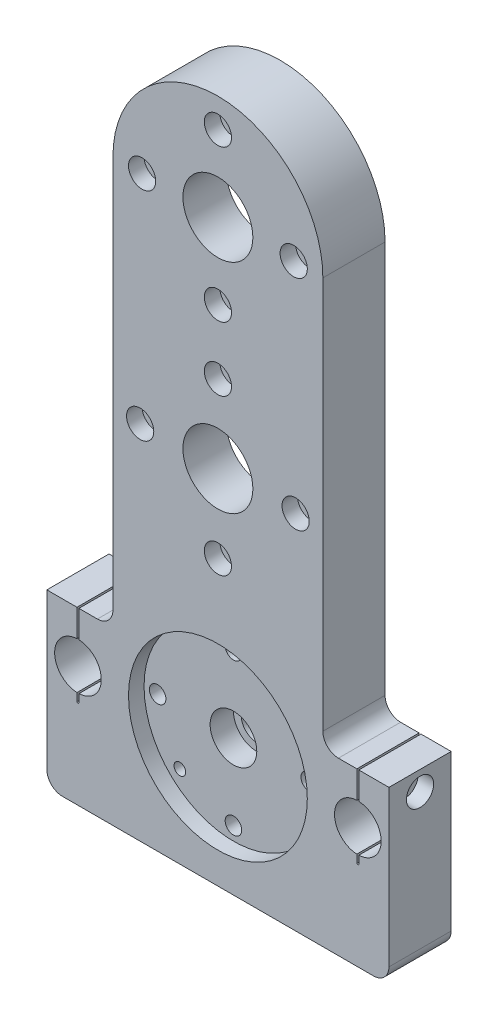
SolidWorks part; units mm, degrees
material "6061 Alloy"
ref_plane "Front" through (0, 0, 0) normal (0, 0, 1) x (1, 0, 0)
ref_plane "Top" through (0, 0, 0) normal (0, 1, 0) x (1, 0, 0)
ref_plane "Right" through (0, 0, 0) normal (1, 0, 0) x (0, 0, -1)
ref_axis "Axis" through (0, 0, -80.9) along (0, 0, 1)
sketch "Bolt circle" plane through (0, 0, 0) normal (0, 0, 1) x (1, 0, 0)
  line L0 (0, 36.5125) -> (0, 25.4) construction
  line L1 (-42.8625, 88.9) -> (-42.8625, -77.7875)
  line L2 (0, 114.3) -> (0, 125.4125) construction
  line L3 (42.8625, 88.9) -> (42.8625, -77.7875)
  line L7 (42.8625, -77.7875) -> (69.85, -77.7875)
  line L12 (-42.8625, -77.7875) -> (-69.85, -77.7875)
  line L30 (69.85, -77.7875) -> (69.85, -147.6375)
  line L31 (69.85, -147.6375) -> (-69.85, -147.6375)
  line L34 (-69.85, -77.7875) -> (-69.85, -147.6375)
  line L35 (0, 0) -> (0, -147.6375) construction
  circle A0 centre (0, 0) radius 36.5125 construction
  circle A1 centre (0, 0) radius 25.4 construction
  circle A2 centre (0, 0) radius 30.9562 construction
  arc A3 (-42.8625, 88.9) -> (42.8625, 88.9) centre (0, 88.9) cw
  circle A4 centre (0, 88.9) radius 14.2748
  circle A5 centre (0, 88.9) radius 36.5125 construction
  circle A6 centre (0, 88.9) radius 25.4 construction
  circle A7 centre (0, 0) radius 14.2748
  circle A8 centre (0, -98.425) radius 36.5125 construction
  circle A9 centre (0, -98.425) radius 6.35
  circle A10 centre (0, 88.9) radius 30.9562 construction
  point P0 (0, -36.5125)
  point P7 (0, 30.9562)
  point P9 (0, -134.9375)
  point P20 (0, 119.8562)
  dimension "D1" = 73.025
  dimension "D2" = 50.8
  dimension "D3" = 69.85
  dimension "D12" = 139.7
  dimension "D5" = 26.9875
  dimension "D13" = 28.5496
  dimension "D18" = 12.7
  dimension "D6" = 88.9
  dimension "D8" = 73.025
  dimension "D9" = 28.5496
  dimension "D10" = 50.8
  dimension "D4" = 98.425
  dimension "D7" = 85.725
  dimension "D17" = 12.7
extrude "Base" add sketch "Bolt circle" along normal mid plane 25.4
hole_wizard "Structure tube connection counterbore" positions "Sketch15" profile "Sketch14" counterbore size "1/4" standard "Ansi Inch" end condition through all
sketch "Sketch15" plane through (0, 0, -12.7) normal (0, 0, -1) x (-1, 0, 0)
  circle A0 centre (0, -98.425) radius 30.9563 construction
  point P1 (0, -67.4688)
  dimension "D1" = 61.9125
sketch "Sketch14" plane through (0, -67.4688, -12.7) normal (1, 0, 0) x (0, 1, 0)
  line L0 (0, 0) -> (0, 25.4)
  line L1 (0, 25.4) -> (3.3782, 25.4)
  line L3 (3.3782, 25.4) -> (3.3782, 6.35)
  line L4 (3.3782, 6.35) -> (5.5562, 6.35)
  line L5 (5.5562, 6.35) -> (5.5562, 0)
  line L7 (5.5562, 0) -> (0, 0)
  line L11 (0, -6.35) -> (0, 107.95) construction
  dimension "Thru Hole Dia." = 6.7564
  dimension "Thru Hole Depth" = 25.4
  dimension "C'Bore Dia." = 11.1125
  dimension "C'Bore Depth" = 6.35
pattern_circular "Structure tube connection counterbore pattern" count 4 over 360 about axis through (0, -98.425, 12.7) along (0, 0, -1) of "Structure tube connection counterbore"
hole_wizard "Spindle connection counterbore" positions "Sketch11" profile "Sketch10" counterbore size "1/4" standard "Ansi Inch" end condition through all
sketch "Sketch11" plane through (0, 0, 12.7) normal (0, 0, 1) x (1, 0, 0)
  circle A0 centre (0, 0) radius 31.75 construction
  point P0 (0, 31.75)
  dimension "D1" = 63.5
sketch "Sketch10" plane through (0, 31.75, 12.7) normal (1, 0, 0) x (0, -1, 0)
  line L0 (0, 0) -> (0, 25.4)
  line L1 (0, 25.4) -> (3.3782, 25.4)
  line L3 (3.3782, 25.4) -> (3.3782, 6.35)
  line L4 (3.3782, 6.35) -> (5.5562, 6.35)
  line L5 (5.5562, 6.35) -> (5.5562, 0)
  line L7 (5.5562, 0) -> (0, 0)
  line L11 (0, -6.35) -> (0, 107.95) construction
  dimension "Thru Hole Dia." = 6.7564
  dimension "Thru Hole Depth" = 25.4
  dimension "C'Bore Dia." = 11.1125
  dimension "C'Bore Depth" = 6.35
pattern_circular "Spindle connection counterbore pattern" count 4 over 360 about axis through (0, 0, 12.7) along (0, 0, -1) of "Spindle connection counterbore"
sketch "Sketch16" plane through (0, 0, 12.7) normal (0, 0, 1) x (1, 0, 0)
  circle A0 centre (0, -98.425) radius 36.5125
  dimension "D1" = 73.025
extrude "Structure tube mounting pocket" cut sketch "Sketch16" against normal blind 6.35
sketch "Sketch17" plane through (0, 0, -12.7) normal (0, 0, -1) x (-1, 0, 0)
  circle A0 centre (0, 0) radius 36.5125
  circle A1 centre (0, -98.425) radius 36.5125 construction
  dimension "D1" = 73.025
extrude "Spindle mounting pocket" cut sketch "Sketch17" against normal blind 7.62
sketch "Sketch18" plane through (0, 0, 6.35) normal (0, 0, 1) x (1, 0, 0)
  circle A0 centre (0, -98.425) radius 9.525
  dimension "D1" = 19.05
extrude "Lead screw through hole" cut sketch "Sketch18" against normal blind 9.525
sketch "Sketch20" plane through (0, 0, 12.7) normal (0, 0, 1) x (1, 0, 0)
  line L1 (57.15, -98.425) -> (-57.15, -98.425) construction
  circle A0 centre (57.15, -98.425) radius 9.525
  circle A1 centre (-57.15, -98.425) radius 9.525
  dimension "D2" = 114.3
  dimension "D3" = 19.05
extrude "Rail mounting pilot_holes" cut sketch "Sketch20" against normal through all
sketch "Sketch27" plane through (0, 0, 6.35) normal (0, 0, 1) x (1, 0, 0)
  line L0 (20.6813, -74.3354) -> (19.6028, -75.5003)
  line L1 (24.176, -77.571) -> (23.0974, -78.7359)
  line L2 (21.8894, -76.5356) -> (-21.8894, -120.3144) construction
  line L3 (20.1421, -74.9178) -> (23.6367, -78.1534) construction
  line L4 (50, 0) -> (-50, 0) construction
  circle A0 centre (-21.8894, -120.3144) radius 2.3813
  arc A1 (24.176, -77.571) -> (20.6813, -74.3354) centre (22.4286, -75.9532) ccw
  arc A2 (23.0974, -78.7359) -> (19.6028, -75.5003) centre (21.3501, -77.1181) cw
  circle A3 centre (21.8894, -76.5356) radius 2.3813 construction
  circle A4 centre (0, -98.425) radius 30.9563 construction
  point P10 (20.1421, -74.9178)
  dimension "D2" = 45
  dimension "D3" = 4.7625
  dimension "D1" = 1.5875
extrude "Alignment_features" cut sketch "Sketch27" against normal blind 6.35
fillet "Generic_rounding_fillet" radius 6.35 4 edges at (42.8625, -77.7875, 0) (-42.8625, -77.7875, 0) (-69.85, -147.6375, 0) (69.85, -147.6375, 0)
sketch "Sketch21" plane through (0, -147.6375, 0) normal (0, -1, 0) x (1, 0, 0)
  line L0 (69.85, 0) -> (-69.85, 0) construction
  line L1 (69.85, 12.7) -> (69.85, -12.7) construction
  line L2 (-69.85, 12.7) -> (-69.85, -12.7) construction
  line L3 (0, -12.7) -> (0, 12.7) construction
  line L4 (-63.5, -12.7) -> (63.5, -12.7) construction
  line L5 (-63.5, 12.7) -> (63.5, 12.7) construction
  circle A0 centre (57.15, 0) radius 4.7625
  circle A1 centre (-57.15, 0) radius 4.7625
  dimension "D1" = 9.525
  dimension "D2" = 114.3
extrude "Point_mount_bores" [suppressed] cut sketch "Sketch21" against normal blind 6.35
sketch "Sketch22" plane through (0, 0, 12.7) normal (0, 0, 1) x (1, 0, 0)
  line L0 (69.85, -77.7875) -> (49.2125, -77.7875) construction
  line L1 (56.7531, -77.7875) -> (57.5469, -77.7875)
  line L2 (56.7531, -77.7875) -> (56.7531, -111.125)
  line L3 (57.15, -111.125) -> (57.15, -98.425) construction
  line L4 (57.5469, -77.7875) -> (57.5469, -111.125)
  line L5 (0, -147.6375) -> (0, 131.7625) construction
  line L6 (-63.5, -147.6375) -> (63.5, -147.6375) construction
  line L7 (-57.15, -111.125) -> (-57.15, -98.425) construction
  line L8 (-57.5469, -77.7875) -> (-57.5469, -111.125)
  line L9 (-56.7531, -77.7875) -> (-56.7531, -111.125)
  line L10 (-56.7531, -77.7875) -> (-57.5469, -77.7875)
  arc A0 (56.7531, -111.125) -> (57.5469, -111.125) centre (57.15, -111.125) ccw
  arc A2 (-56.7531, -111.125) -> (-57.5469, -111.125) centre (-57.15, -111.125) cw
  arc A3 (42.8625, 88.9) -> (-42.8625, 88.9) centre (0, 88.9) ccw construction
  dimension "D1" = 0.7937
  dimension "D2" = 12.7
extrude "Flexure_clamp_slits" cut sketch "Sketch22" against normal through all
hole_wizard "Flexure_clamp_counterbore" positions "Sketch24" profile "Sketch23" counterbore size "1/4" standard "Ansi Inch" end condition up to next
sketch "Sketch24" plane through (69.85, 0, 0) normal (1, 0, 0) x (0, 0, -1)
  line L0 (0, 50) -> (0, -50) construction
  line L1 (-12.7, -77.7875) -> (12.7, -77.7875) construction
  point P0 (0, -85.725)
  dimension "D1" = 7.9375
sketch "Sketch23" plane through (69.85, -85.725, 0) normal (0, 1, 0) x (0, 0, -1)
  line L0 (0, 0) -> (0, 12.3031)
  line L1 (0, 12.3031) -> (3.3782, 12.3031)
  line L3 (3.3782, 12.3031) -> (3.3782, 6.35)
  line L4 (3.3782, 6.35) -> (5.5562, 6.35)
  line L5 (5.5562, 6.35) -> (5.5562, 0)
  line L7 (5.5562, 0) -> (0, 0)
  line L11 (0, -6.35) -> (0, 107.95) construction
  dimension "Thru Hole Dia." = 6.7564
  dimension "Thru Hole Depth" = 12.3031
  dimension "C'Bore Dia." = 11.1125
  dimension "C'Bore Depth" = 6.35
hole_wizard "Flexure_clamp_threads" positions "Sketch26" profile "Sketch25" tap size "1/4-20" standard "Ansi Inch"
sketch "Sketch26" plane through (56.7531, 0, 0) normal (1, 0, 0) x (0, 0, -1)
  point P1 (0, -85.725)
sketch "Sketch25" plane through (56.7531, -85.725, 0) normal (0, 1, 0) x (0, 0, -1)
  line L0 (0, 0) -> (0, 18.0438)
  line L1 (0, 18.0438) -> (2.5527, 16.51)
  line L2 (2.5527, 16.51) -> (2.5527, 0)
  line L5 (2.5527, 0) -> (0, 0)
  line L10 (0, 18.0438) -> (-2.5527, 16.51) construction
  line L11 (0, -6.35) -> (0, 107.95) construction
  dimension "Tap Drill Dia." = 5.1054
  dimension "Tap Drill Depth" = 16.51
  dimension "Drill Angle" = 118
cosmetic thread "Hole Thread2" parameters "D1"=12.7, "D2"=6.35
mirror "Flexure_clamp_fastener_holes" about plane through (0, 0, 0) normal (1, 0, 0) of "Flexure_clamp_counterbore", "Flexure_clamp_threads"
hole_wizard "wood_spindle_CBORE" positions "Sketch28" profile "Sketch29" counterbore size "1/4" standard "ANSI Inch" end condition through all
sketch "Sketch28" plane through (0, 0, 12.7) normal (0, 0, 1) x (1, 0, 0)
  point P0 (0, 119.8562)
sketch "Sketch29" plane through (0, 119.8562, 12.7) normal (1, 0, 0) x (0, -1, 0)
  line L0 (0, 0) -> (0, 25.4)
  line L1 (0, 25.4) -> (3.3782, 25.4)
  line L3 (3.3782, 25.4) -> (3.3782, 6.35)
  line L4 (3.3782, 6.35) -> (5.5562, 6.35)
  line L5 (5.5562, 6.35) -> (5.5562, 0)
  line L7 (5.5562, 0) -> (0, 0)
  line L11 (0, -6.35) -> (0, 107.95) construction
  dimension "Thru Hole Dia." = 6.7564
  dimension "Thru Hole Depth" = 25.4
  dimension "C'Bore Dia." = 11.1125
  dimension "C'Bore Depth" = 6.35
pattern_circular "CirPattern1" count 4 over 360 about axis through (0, 88.9, 12.7) along (0, 0, -1) of "wood_spindle_CBORE"
sketch "Sketch30" plane through (0, 0, -12.7) normal (0, 0, -1) x (-1, 0, 0)
  circle A0 centre (0, 88.9) radius 36.5125
  dimension "D1" = 73.025
extrude "Cut-Extrude1" cut sketch "Sketch30" against normal blind 7.62
